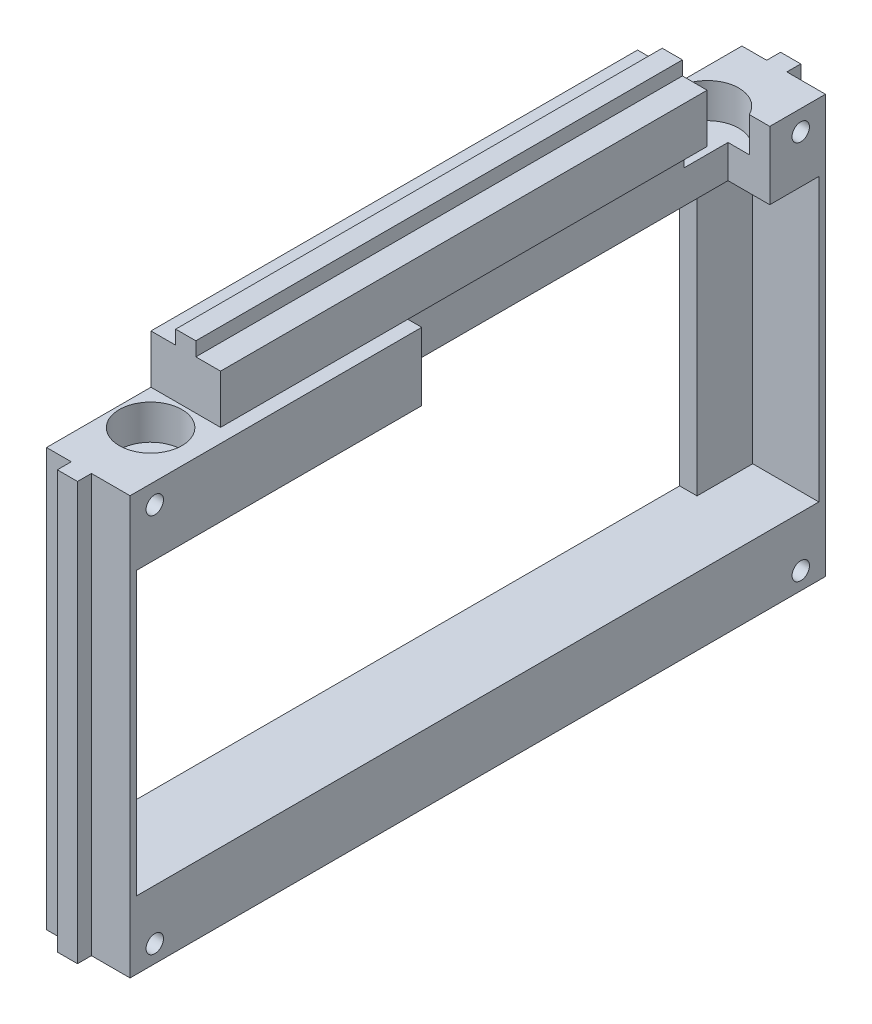
SolidWorks part; units mm, degrees
ref_plane "Front Plane" through (0, 0, 0) normal (0, 0, 1) x (1, 0, 0)
ref_plane "Top Plane" through (0, 0, 0) normal (0, 1, 0) x (1, 0, 0)
ref_plane "Right Plane" through (0, 0, 0) normal (1, 0, 0) x (0, 0, -1)
sketch "Esquisse1" plane through (0, 0, 0) normal (0, 0, 1) x (1, 0, 0)
  line L0 (0, 60) -> (12, 60)
  line L1 (12, 60) -> (12, 0)
  line L2 (12, 0) -> (0, 0)
  line L7 (0, 0) -> (0, 60)
  dimension "D1" = 12
  dimension "D2" = 60
  dimension "D6" = 12
extrude "Main" add sketch "Esquisse1" along normal mid plane 99.9
sketch "Esquisse2" plane through (12, 0, 0) normal (1, 0, 0) x (0, 0, -1)
  line L1 (-46.4, 2.5) -> (46.4, 2.5) construction
  line L2 (-49.95, 0) -> (49.95, 0) construction
  line L3 (-49.95, 60) -> (49.95, 60) construction
  circle A0 centre (46.4, 2.5) radius 1.25
  circle A1 centre (-46.4, 2.5) radius 1.25
  circle A2 centre (46.4, 57.1) radius 1.25
  circle A3 centre (-46.4, 57.1) radius 1.25
  point P8 (0, 60)
  point P9 (0, 2.5)
  point P14 (0, 0)
  point P15 (0, 0)
  point P16 (44.9854, 56.9)
  dimension "D1" = 92.8
  dimension "D4" = 54.6
  dimension "D3" = 2.5
  dimension "D2" = 2.5
extrude "HolesFixForLCD" cut sketch "Esquisse2" against normal through all
sketch "Sketch1" plane through (12, 0, 0) normal (1, 0, 0) x (0, 0, -1)
  line L0 (-49.95, 60) -> (49.95, 60) construction
  line L1 (49, 9.75) -> (-49, 9.75)
  line L2 (49, 9.75) -> (49, 50.25)
  line L3 (49, 50.25) -> (-49, 50.25)
  line L4 (-49, 9.75) -> (-49, 50.25)
  line L7 (49.95, 0) -> (49.95, 60) construction
  point P4 (49, 30)
  point P5 (49.95, 30)
  point P6 (0, 60)
  point P11 (0, 0)
  point P12 (0, 50.25)
  dimension "D1" = 98
  dimension "D4" = 40.5
extrude "LCDWindowHole" cut sketch "Sketch1" against normal through all
sketch "Sketch6" plane through (0, 60, 0) normal (0, 1, 0) x (1, 0, 0)
  line L0 (12, 49.95) -> (0, 49.95) construction
  line L1 (3.55, 51.95) -> (6.45, 51.95)
  line L2 (3.55, 51.95) -> (3.55, 49.95)
  line L3 (3.55, 49.95) -> (6.45, 49.95)
  line L4 (6.45, 51.95) -> (6.45, 49.95)
  line L6 (0, -49.95) -> (0, 49.95) construction
  line L7 (12, -49.95) -> (0, -49.95) construction
  line L8 (3.55, -49.95) -> (6.45, -49.95)
  line L9 (3.55, -49.95) -> (3.55, -51.95)
  line L10 (3.55, -51.95) -> (6.45, -51.95)
  line L11 (6.45, -49.95) -> (6.45, -51.95)
  dimension "D1" = 2
  dimension "D2" = 3.55
  dimension "D3" = 2.9
extrude "MakerBeamRail" add sketch "Sketch6" against normal up to surface (60 mm away) up to face at (6, 0, 0)
sketch "Sketch7" plane through (12, 0, 0) normal (1, 0, 0) x (0, 0, -1)
  line L0 (-49.95, 60) -> (49.95, 60) construction
  line L1 (-8.05, 60) -> (41.95, 60)
  line L2 (-8.05, 60) -> (-8.05, 50.25)
  line L3 (-8.05, 50.25) -> (41.95, 50.25)
  line L4 (41.95, 60) -> (41.95, 50.25)
  line L5 (49.95, 0) -> (49.95, 60) construction
  line L6 (49, 50.25) -> (-49, 50.25) construction
  point P8 (-4.0758, 50.25)
  dimension "D1" = 8
  dimension "D2" = 50
extrude "LCDPinsHoles" cut sketch "Sketch7" against normal blind 6
sketch "Sketch8" plane through (0, 0, 0) normal (-1, 0, 0) x (0, 0, 1)
  line L0 (49, 9.75) -> (-49, 9.75) construction
  line L1 (-49, 50.25) -> (-41, 50.25)
  line L2 (-49, 50.25) -> (-49, 9.75)
  line L3 (-49, 9.75) -> (-41, 9.75)
  line L4 (-41, 50.25) -> (-41, 9.75)
  line L6 (49, 50.25) -> (41, 50.25)
  line L7 (49, 50.25) -> (49, 9.75)
  line L8 (49, 9.75) -> (41, 9.75)
  line L9 (41, 50.25) -> (41, 9.75)
  dimension "D1" = 8
extrude "Reinforcement" add sketch "Sketch8" against normal blind 2.5 separate body
sketch "Sketch9" plane through (0, 60, 0) normal (0, 1, 0) x (1, 0, 0)
  line L0 (5, 40) -> (5, -40) construction
  line L1 (0, -49.95) -> (0, 49.95) construction
  circle A0 centre (5, -40) radius 4.5
  circle A1 centre (5, 40) radius 4.5
  point P4 (5, 0)
  point P9 (5, -39.89)
  dimension "D1" = 9
  dimension "D2" = 80
  dimension "D3" = 5
extrude "Cut-Extrude2" cut sketch "Sketch9" against normal blind 5
sketch "Sketch10" plane through (0, 0, 0) normal (-1, 0, 0) x (0, 0, 1)
  line L0 (49.95, 60) -> (-49.95, 60) construction
  line L1 (-34.95, 60) -> (34.95, 60)
  line L2 (-34.95, 60) -> (-34.95, 67)
  line L3 (-34.95, 67) -> (34.95, 67)
  line L4 (34.95, 60) -> (34.95, 67)
  point P7 (0, 67)
  dimension "D1" = 7
  dimension "D2" = 69.9
extrude "Boss-Extrude3" add sketch "Sketch10" against normal blind 10 separate body
sketch "Sketch11" plane through (0, 67, 0) normal (0, 1, 0) x (1, 0, 0)
  line L0 (10, 34.95) -> (0, 34.95) construction
  line L1 (6.45, 34.95) -> (3.55, 34.95)
  line L2 (6.45, 34.95) -> (6.45, -34.95)
  line L3 (6.45, -34.95) -> (3.55, -34.95)
  line L4 (3.55, 34.95) -> (3.55, -34.95)
  line L5 (10, -34.95) -> (0, -34.95) construction
  line L6 (0, -34.95) -> (0, 34.95) construction
  dimension "D1" = 3.55
  dimension "D2" = 2.9
extrude "Boss-Extrude4" add sketch "Sketch11" along normal blind 2
